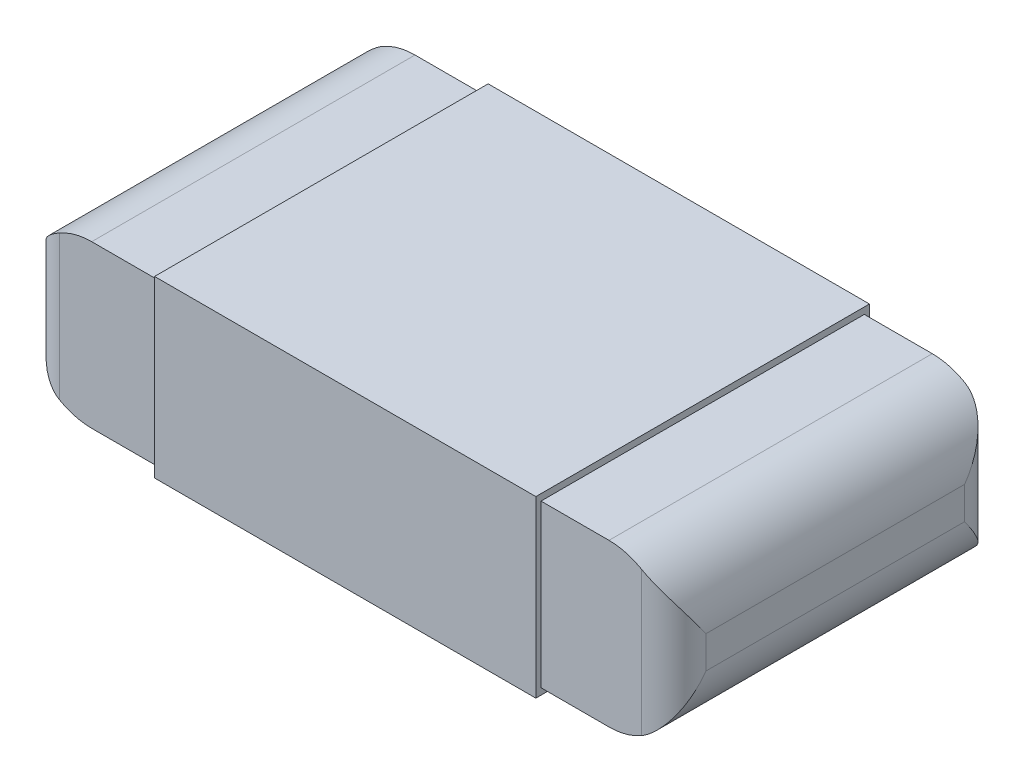
SolidWorks part; units mm, degrees
ref_plane "Plan de face" through (0, 0, 0) normal (0, 0, 1) x (1, 0, 0)
ref_plane "Plan de dessus" through (0, 0, 0) normal (0, 1, 0) x (1, 0, 0)
ref_plane "Plan de droite" through (0, 0, 0) normal (1, 0, 0) x (0, 0, -1)
sketch "Esquisse1" plane through (0, 0, 0) normal (0, 1, 0) x (1, 0, 0)
  line L1 (0.9, -0.5) -> (-0.9, -0.5)
  line L2 (1, -0.4) -> (1, 0.4)
  line L3 (0.9, 0.5) -> (-0.9, 0.5)
  line L4 (-1, -0.4) -> (-1, 0.4)
  line L5 (1, -0.5) -> (-1, 0.5) construction
  line L6 (1, 0.5) -> (-1, -0.5) construction
  arc A0 (1, 0.4) -> (0.9, 0.5) centre (0.9, 0.4) ccw
  arc A1 (0.9, -0.5) -> (1, -0.4) centre (0.9, -0.4) ccw
  arc A2 (-0.9, -0.5) -> (-1, -0.4) centre (-0.9, -0.4) cw
  arc A3 (-0.9, 0.5) -> (-1, 0.4) centre (-0.9, 0.4) ccw
  point P0 (0, 0)
  dimension "D3" = 0.1
  dimension "D1" = 2
  dimension "D2" = 1
extrude "Boss.-Extru.1" add sketch "Esquisse1" along normal blind 0.5
sketch "Esquisse2" plane through (0, 0.5, 0) normal (0, 1, 0) x (1, 0, 0)
  line L1 (0.5897, -0.5159) -> (-0.5897, -0.5159)
  line L2 (0.5897, -0.5159) -> (0.5897, 0.5159)
  line L3 (0.5897, 0.5159) -> (-0.5897, 0.5159)
  line L4 (-0.5897, -0.5159) -> (-0.5897, 0.5159)
  line L5 (0.5897, -0.5159) -> (-0.5897, 0.5159) construction
  line L6 (0.5897, 0.5159) -> (-0.5897, -0.5159) construction
  point P0 (0, 0)
extrude "Boss.-Extru.2" add sketch "Esquisse2" along normal blind 0.02 and the other way blind 0.52
fillet "Congé2" radius 0.2 3 edges at (-0.9707, 0, 0.4707) (-1, 0, 0) (-0.9707, 0, -0.4707)
fillet "Congé3" radius 0.2 3 edges at (-0.9707, 0.5, -0.4707) (-1, 0.5, 0) (-0.9707, 0.5, 0.4707)
fillet "Congé4" radius 0.2 3 edges at (0.9707, 0.5, 0.4707) (1, 0.5, 0) (0.9707, 0.5, -0.4707)
fillet "Congé5" radius 0.2 3 edges at (0.9707, 0, -0.4707) (1, 0, 0) (0.9707, 0, 0.4707)
